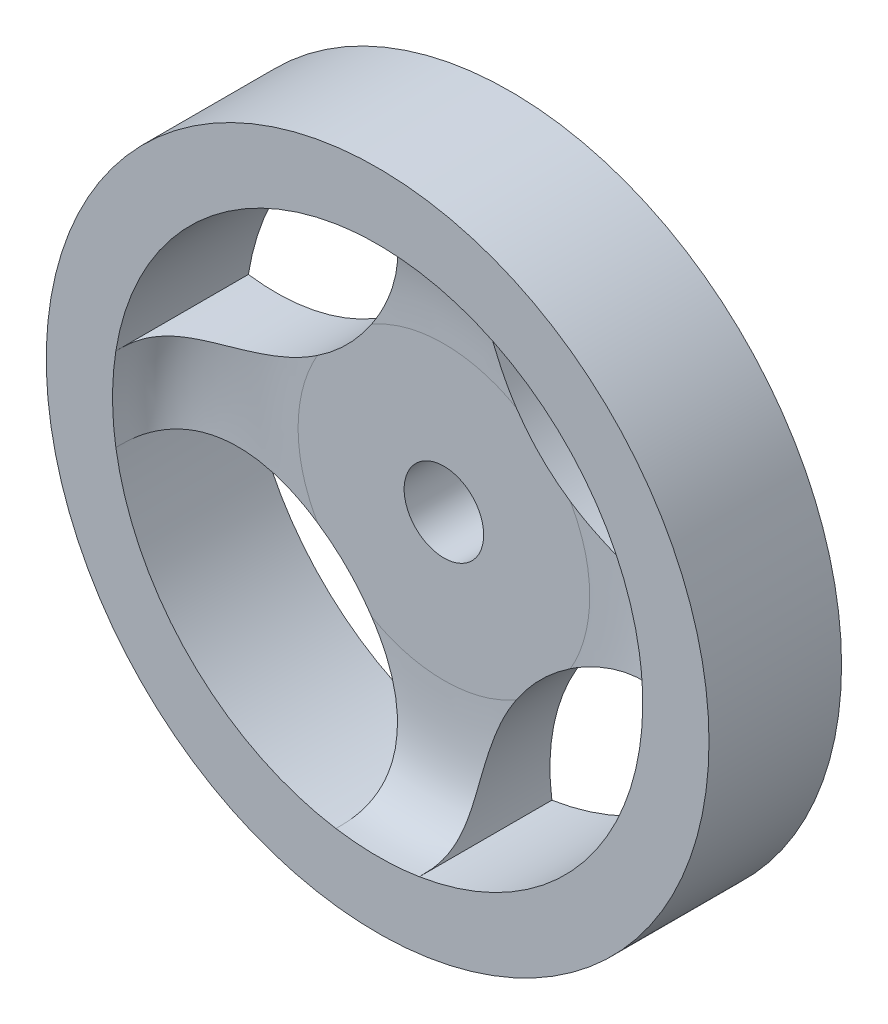
SolidWorks part; units mm, degrees
ref_plane "Front Plane" through (0, 0, 0) normal (0, 0, 1) x (1, 0, 0)
ref_plane "Top Plane" through (0, 0, 0) normal (0, 1, 0) x (1, 0, 0)
ref_plane "Right Plane" through (0, 0, 0) normal (1, 0, 0) x (0, 0, -1)
ref_plane "Plane1" through (0, 0, 10) normal (0, 0, 1) x (1, 0, 0)
sketch "Sketch1" plane through (0, 0, 10) normal (0, 0, 1) x (1, 0, 0)
  line L0 (4.4964, 9.7438) -> (4.4964, 59.7438)
  line L1 (-20.5036, 34.7438) -> (29.4964, 34.7438)
  arc A0 (29.4964, 34.7438) -> (4.4964, 59.7438) centre (4.4964, 34.7438) ccw
  circle A1 centre (4.4964, 34.7438) radius 20
  circle A2 centre (4.4964, 34.7438) radius 3
  circle A3 centre (4.4964, 34.7438) radius 6
  arc A4 (7.6435, 54.4946) -> (24.2472, 37.891) centre (22.1741, 52.4215) ccw
  arc A5 (1.3492, 54.4946) -> (-15.2544, 37.891) centre (-13.1813, 52.4215) cw
  arc A6 (4.4964, 9.7438) -> (4.4964, 59.7438) centre (4.4964, 34.7438) cw
  arc A7 (1.3492, 14.993) -> (-15.2544, 31.5967) centre (-13.1813, 17.0661) ccw
  arc A8 (7.6435, 14.993) -> (24.2472, 31.5967) centre (22.1741, 17.0661) cw
  arc A9 (29.4964, 34.7438) -> (4.4964, 9.7438) centre (4.4964, 34.7438) cw
extrude "Boss-Extrude1" add sketch "Sketch1" along normal blind 5 contours A6 L1 A1 L0 | A6 L0 A1 L1 | A9 L1 A1 L0 | A1 L1 A0 L0 | L0 A3 L1 A2 | L1 A3 L0 A2 | L0 A3 L1 A2 | L1 A3 L0 A2 | A1 A5 L1 A3 L0 | A4 A1 L0 A3 L1 | A7 A1 L0 A3 L1 | A1 A8 L1 A3 L0 region at (-9.8865, 20.3609, 10) region at (18.8793, 20.3609, 10) region at (-2.4342, 27.8132, 10) region at (11.427, 27.8132, 10) region at (-9.8865, 49.1267, 10) region at (18.8793, 49.1267, 10) region at (1.5255, 31.7729, 10) region at (7.4673, 31.7729, 10) region at (-2.4342, 41.6744, 10) region at (11.427, 41.6744, 10) region at (1.5255, 37.7147, 10) region at (7.4673, 37.7147, 10)
extrude "Boss-Extrude3" add sketch "Sketch1<4>" along normal blind 10 contours A6 L1 A1 L0 | A6 L0 A1 L1 | A9 L1 A1 L0 | A1 L1 A0 L0 region at (-9.8865, 20.3609, 10) region at (18.8793, 20.3609, 10) region at (-9.8865, 49.1267, 10) region at (18.8793, 49.1267, 10)
sketch "Sketch1<4>" plane through (0, 0, 10) normal (0, 0, 1) x (1, 0, 0) same geometry as "Sketch1"
fillet "Fillet2" radius 9 4 edges at (4.4964, 14.7438, 15) (24.4964, 34.7438, 15) (4.4964, 54.7438, 15) (-15.5036, 34.7438, 15) curvature continuous yes second distance 5 first distance on face at (4.4964, 34.7438, 15)
